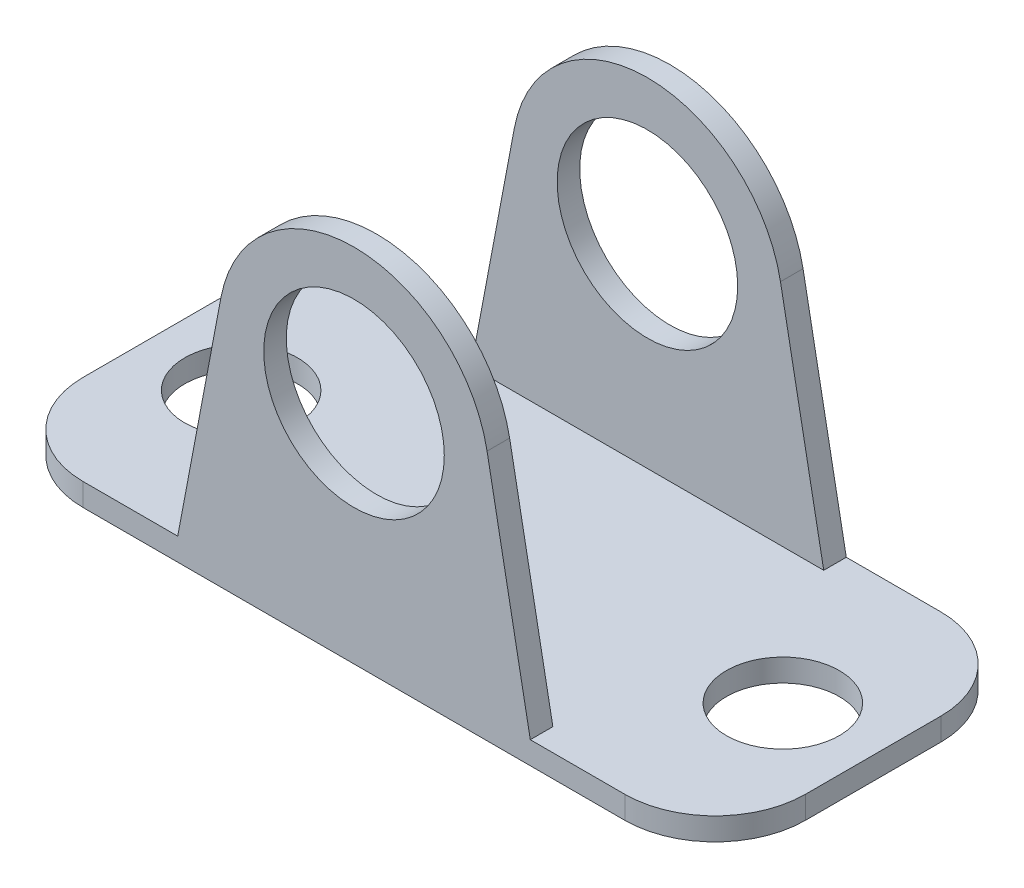
SolidWorks part; units mm, degrees
ref_plane "前基準面" through (0, 0, 0) normal (0, 0, 1) x (1, 0, 0)
ref_plane "上基準面" through (0, 0, 0) normal (0, 1, 0) x (1, 0, 0)
ref_plane "右基準面" through (0, 0, 0) normal (1, 0, 0) x (0, 0, -1)
sketch "草圖1" plane through (0, 0, 0) normal (0, 0, 1) x (1, 0, 0)
  line L0 (0, 0) -> (0, 5) construction
  line L1 (-4, 0) -> (4, 0)
  line L2 (4, 0) -> (2.9476, 5.5581)
  line L3 (2.9476, 0.7986) -> (2.9476, -1.411) construction
  line L4 (-4, 0) -> (-2.9476, 5.5581)
  line L5 (-3.9053, 0.5) -> (3.9053, 0.5)
  arc A0 (2.9476, 5.5581) -> (-2.9476, 5.5581) centre (0, 5) ccw
  circle A1 centre (0, 5) radius 2
  dimension "D3" = 3
  dimension "D2" = 5
  dimension "D5" = 4
  dimension "D1" = 8
  dimension "D4" = 0.5
extrude "填料-伸長1" add sketch "草圖1" along normal blind 0.5 contours L2 A0 L4 L5 | L5 L4 L1 L2 region at (0, 0.249, 0) region at (-3.3201, 3.0089, 0)
extrude "填料-伸長2" add sketch "草圖1<3>" against normal blind 3 contours L5 L4 L1 L2 region at (0, 0.249, 0)
sketch "草圖1<3>" plane through (0, 0, 0) normal (0, 0, 1) x (1, 0, 0) same geometry as "草圖1"
mirror "鏡射1" about plane through (0, 0, -3) normal (0, 0, 1) of bodies 103
sketch "草圖4" plane through (0, 0, 0) normal (1, 0, 0) x (0, 0, -1)
  line L0 (-0.5, 0) -> (-0.5, 5.5581) construction
  line L1 (-0.5, 0.5) -> (6.5, 0.5)
  line L2 (-0.5, 0.5) -> (-0.5, 0)
  line L3 (-0.5, 0) -> (6.5, 0)
  line L4 (6.5, 0.5) -> (6.5, 0)
  line L5 (6, 0.5) -> (0, 0.5) construction
extrude "填料-伸長3" add sketch "草圖4" along normal mid plane 16
hole_wizard "Ø2.5mm 定位孔1" positions "草圖2" profile "草圖3" hole size "Ø2.5" standard "ISO" end condition up to next
sketch "草圖2" plane through (0, 0.5, 0) normal (0, 1, 0) x (1, 0, 0)
  line L0 (0, 0) -> (0, 3) construction
  line L1 (0, 3) -> (8, 3) construction
  line L3 (8, 6.5) -> (8, -0.5) construction
  point P0 (-6, 3)
  point P14 (6, 3)
  point P16 (0, 6.25)
  point P17 (0, 0)
  point P18 (0, 3.0071)
  point P19 (7.5, 3)
  dimension "D1" = 12
sketch "草圖3" plane through (-6, 0.5, -3) normal (1, 0, 0) x (0, 0, 1)
  line L0 (0, 0) -> (0, 0.5)
  line L1 (0, 0.5) -> (1.25, 0.5)
  line L2 (1.25, 0.5) -> (1.25, 0)
  line L5 (1.25, 0) -> (0, 0)
  line L11 (0, -6.35) -> (0, 107.95) construction
  dimension "貫穿孔直徑" = 2.5
  dimension "貫穿孔深度" = 0.5
fillet "圓角1" radius 2 4 edges at (8, 0.25, -6.5) (8, 0.25, 0.5) (-8, 0.25, -6.5) (-8, 0.25, 0.5)
